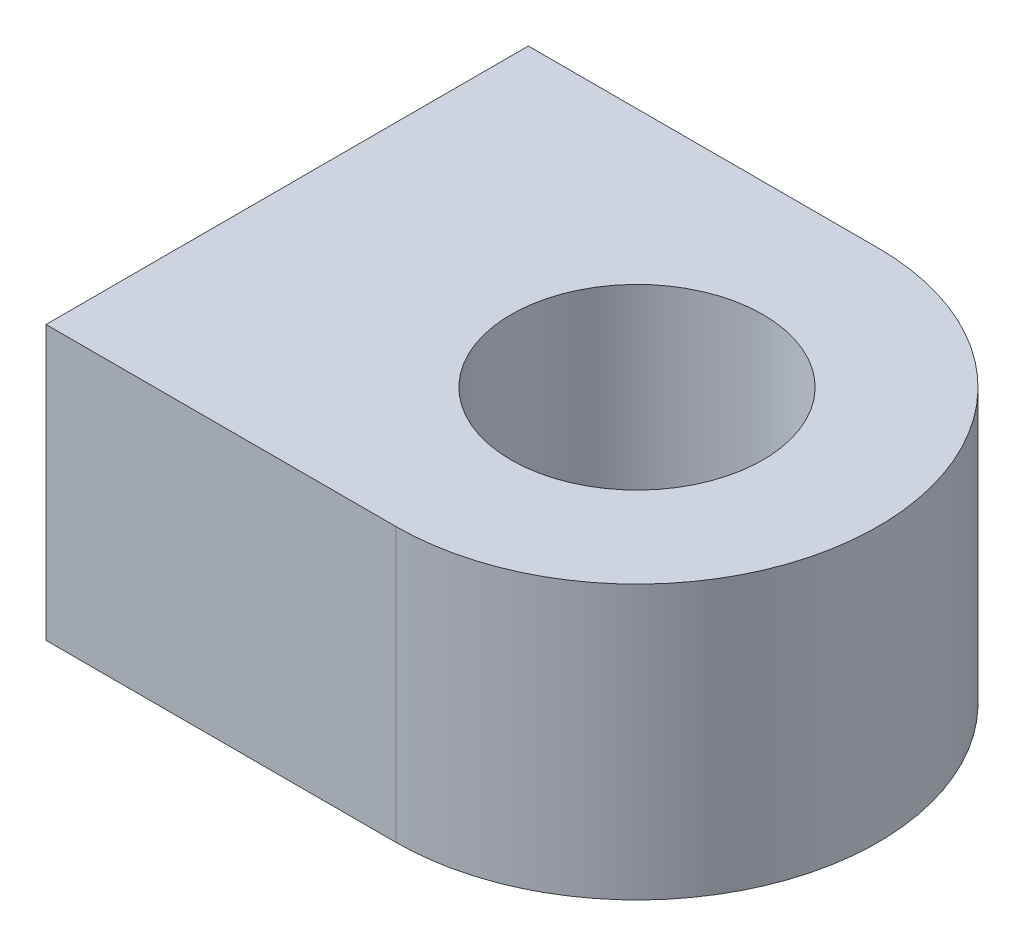
SolidWorks part; units mm, degrees
ref_plane "Front Plane" through (0, 0, 0) normal (0, 0, 1) x (1, 0, 0)
ref_plane "Top Plane" through (0, 0, 0) normal (0, 1, 0) x (1, 0, 0)
ref_plane "Right Plane" through (0, 0, 0) normal (1, 0, 0) x (0, 0, -1)
sketch "Sketch1" plane through (0, 0, 0) normal (0, 1, 0) x (1, 0, 0)
  circle A0 centre (0, 0) radius 2.2225
  circle A1 centre (0, 0) radius 4.1275
  dimension "D1" = 4.445
  dimension "D2" = 1.905
extrude "Boss-Extrude1" add sketch "Sketch1" along normal blind 5.08 contours A1 A0 region at (-4.0108, 0, 0)
sketch "Sketch2" plane through (0, 0, 0) normal (0, -1, 0) x (1, 0, 0)
  circle A1 centre (0, 0) radius 4.1275
  circle A2 centre (0, 0) radius 4.1275
  dimension "D1" = 0
extrude "Boss-Extrude2" add sketch "Sketch2" against normal blind 0.762
sketch "Sketch3" plane through (0, 5.08, 0) normal (0, 1, 0) x (1, 0, 0)
  line L1 (-6.1722, -4.2545) -> (-6.1722, 4.2545)
  line L2 (0, -4.1275) -> (-6.1722, -4.1275)
  line L3 (0, 4.1275) -> (-6.1722, 4.1275)
  circle A1 centre (0, 0) radius 4.1275
  circle A2 centre (0, 0) radius 4.1275
  circle M3 centre (0, 0) radius 4.1275
  dimension "D1" = 0
extrude "Boss-Extrude3" add sketch "Sketch3" against normal up to surface (5.08 mm away) contours L3 L1 L2 M3 region at (-4.5622, 5.08, 0)
sketch "Sketch4" plane through (0, 5.08, 0) normal (0, 1, 0) x (1, 0, 0)
  line L3 (0, 4.1275) -> (-6.1722, 4.1275)
  line L4 (-6.1722, 4.1275) -> (-6.1722, -4.1275)
  line L5 (-6.1722, -4.1275) -> (0, -4.1275)
  line L6 (0, 4.1275) -> (-6.1722, 4.1275)
  line L7 (-6.1722, 4.1275) -> (-6.1722, -4.1275)
  line L8 (-6.1722, -4.1275) -> (0, -4.1275)
  line L22 (6.1722, 25.2998) -> (-48.0166, 25.2998)
  line L23 (-48.0166, 25.2998) -> (-48.0166, -0.3542)
  line L24 (-45.4766, -2.8942) -> (-22.0218, -2.8942)
  line L25 (-22.0218, -2.8942) -> (-22.0218, -36.3262)
  line L26 (-19.4818, -38.8662) -> (6.1722, -38.8662)
  line L27 (6.1722, -38.8662) -> (6.1722, 25.2998)
  line L28 (0, -30.1653) -> (-6.1722, -30.1653)
  line L29 (-6.1722, -30.1653) -> (-6.1722, -38.8662)
  line L30 (-6.1722, -38.8662) -> (6.1722, -38.8662)
  line L31 (6.1722, -38.8662) -> (6.1722, 12.9554)
  line L32 (6.1722, 12.9554) -> (-6.1722, 12.9554)
  line L33 (-6.1722, 12.9554) -> (-6.1722, 4.2545)
  line L34 (-6.1722, 4.2545) -> (0, 4.2545)
  line L35 (0, -4.2545) -> (-6.1722, -4.2545)
  line L36 (-6.1722, -4.2545) -> (-6.1722, -21.6563)
  line L37 (-6.1722, -21.6563) -> (0, -21.6563)
  line L38 (-6.1722, -4.2545) -> (-6.1722, -4.1275)
  line L39 (-6.1722, 4.1275) -> (-6.1722, 4.2545)
  arc A1 (0, -4.1275) -> (0, 4.1275) centre (0, 0) ccw
  arc A2 (0, -4.1275) -> (0, 4.1275) centre (0, 0) ccw
  arc A6 (-48.0166, -0.3542) -> (-45.4766, -2.8942) centre (-45.4766, -0.3542) ccw
  arc A7 (-22.0218, -36.3262) -> (-19.4818, -38.8662) centre (-19.4818, -36.3262) ccw
  arc A8 (0, -30.1653) -> (0, -21.6563) centre (0, -25.9108) ccw
  arc A9 (0, -4.2545) -> (0, 4.2545) centre (0, 0) ccw
  arc M6 (0, -4.1275) -> (0, 4.1275) centre (0, 0) ccw
  line M7 (0, 4.1275) -> (-6.1722, 4.1275)
  line M9 (-6.1722, -4.1275) -> (0, -4.1275)
  dimension "D1" = 0
extrude "Boss-Extrude5" add sketch "Sketch4" against normal up to surface (5.08 mm away) contours L35 A9 L34 L39 L38 M7 M6 M9 region at (-3.0861, 5.08, -4.141)
sketch "Sketch5" plane through (0, 5.08, 0) normal (0, 1, 0) x (1, 0, 0)
  line L3 (-6.1722, 4.2545) -> (-6.1722, -4.2545)
  line L4 (-6.1722, -4.2545) -> (0, -4.2545)
  line L5 (0, 4.2545) -> (-6.1722, 4.2545)
  line L6 (-6.1722, 4.2545) -> (-6.1722, -4.2545)
  line L7 (-6.1722, -4.2545) -> (0, -4.2545)
  line L8 (0, 4.2545) -> (-6.1722, 4.2545)
  arc A1 (0, -4.2545) -> (0, 4.2545) centre (0, 0) ccw
  arc A2 (0, -4.2545) -> (0, 4.2545) centre (0, 0) ccw
  dimension "D1" = 0
extrude "Cut-Extrude1" cut sketch "Sketch5" against normal blind 0.254
